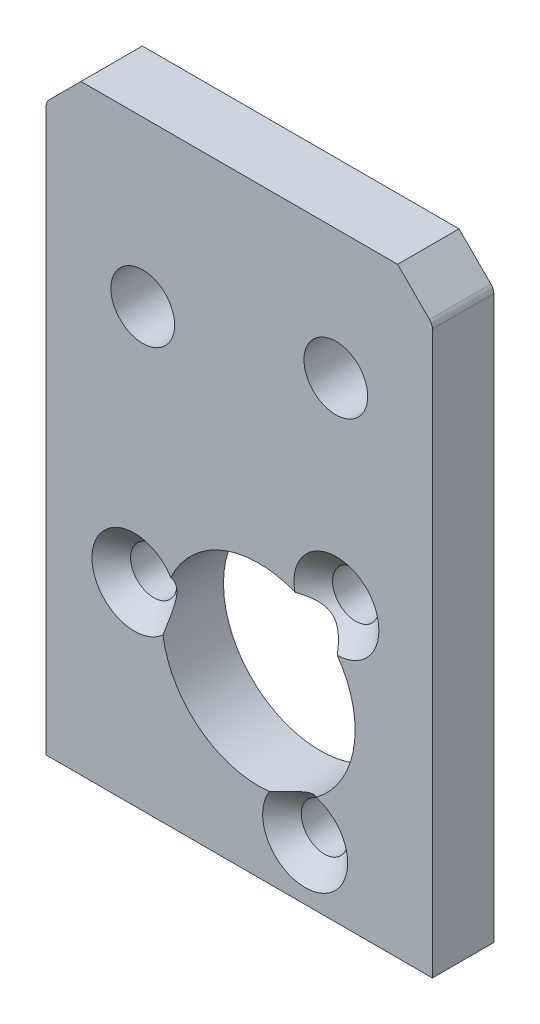
SolidWorks part; units mm, degrees
ref_plane "Front Plane" through (0, 0, 0) normal (0, 0, 1) x (1, 0, 0)
ref_plane "Top Plane" through (0, 0, 0) normal (0, 1, 0) x (1, 0, 0)
ref_plane "Right Plane" through (0, 0, 0) normal (1, 0, 0) x (0, 0, -1)
sketch "Sketch1" plane through (0, 0, 0) normal (0, 0, 1) x (1, 0, 0)
  line L0 (15, 31.5008) -> (15, 0) construction
  line L1 (0, 0) -> (20, 0)
  line L2 (0, 0) -> (0, 31.11)
  line L4 (20, 0) -> (20, 31.11)
  line L5 (5, 31.11) -> (5, 0) construction
  line L6 (0, 31.11) -> (20, 31.11)
  arc A2 (15.0728, 12.0104) -> (12.8801, 13.743) centre (15.03, 14.21) ccw
  arc A3 (6.4499, 11.1828) -> (6.049, 8.4114) centre (4.57, 10.04) ccw
  arc A4 (11.5537, 4.1408) -> (13.9699, 5.0876) centre (13.41, 2.96) ccw
  circle A7 centre (15.03, 14.21) radius 1.2
  circle A8 centre (4.57, 10.04) radius 1.2
  circle A9 centre (13.41, 2.96) radius 1.2
  circle A10 centre (11, 9.11) radius 5
  circle A11 centre (15, 24.41) radius 1.65
  circle A12 centre (5, 22.61) radius 1.65
  dimension "D3" = 3.3
  dimension "D4" = 24.41
  dimension "D5" = 22.61
  dimension "D1" = 31.11
  dimension "D2" = 31.11
extrude "Boss-Extrude2" add sketch "Sketch1" against normal blind 3.18 contours A11 | A12 | L2 L1 L4 L6 | A7 | A10 | A8 | A9 region at (15, 24.41, 0) region at (5, 22.61, 0)
hole_wizard "CSK for M2 Flat Head Machine Screw1" positions "Sketch10" profile "Sketch11" countersink size "M2" standard "ANSI Metric"
sketch "Sketch10" plane through (0, 0, 0) normal (0, 0, 1) x (1, 0, 0)
  point P0 (4.57, 10.04)
  point P3 (15.03, 14.21)
  point P6 (13.41, 2.96)
sketch "Sketch11" plane through (4.57, 10.04, 0) normal (1, 0, 0) x (0, -1, 0)
  line L0 (0, 0) -> (0, 4.23)
  line L1 (0, 4.23) -> (1.2, 3.509)
  line L2 (1.2, 3.509) -> (1.2, 1)
  line L3 (1.2, 1) -> (2.2, 0)
  line L5 (2.2, 0) -> (0, 0)
  line L6 (-1.2, 1) -> (-2.2, 0) construction
  line L10 (0, 4.23) -> (-1.2, 3.509) construction
  line L11 (0, -6.35) -> (0, 107.95) construction
  dimension "Hole Dia." = 2.4
  dimension "Hole Depth" = 4.23
  dimension "Near C'Sink Dia." = 4.4
  dimension "Near C'Sink Angle" = 90
  dimension "Drill Angle" = 118
chamfer "Chamfer1" distance 1.8 angle 45 2 edges at (0, 31.11, -1.59) (20, 31.11, -1.59)
fillet "Fillet1" radius 0.5 2 edges at (20, 29.31, -1.59) (0, 29.31, -1.59)
